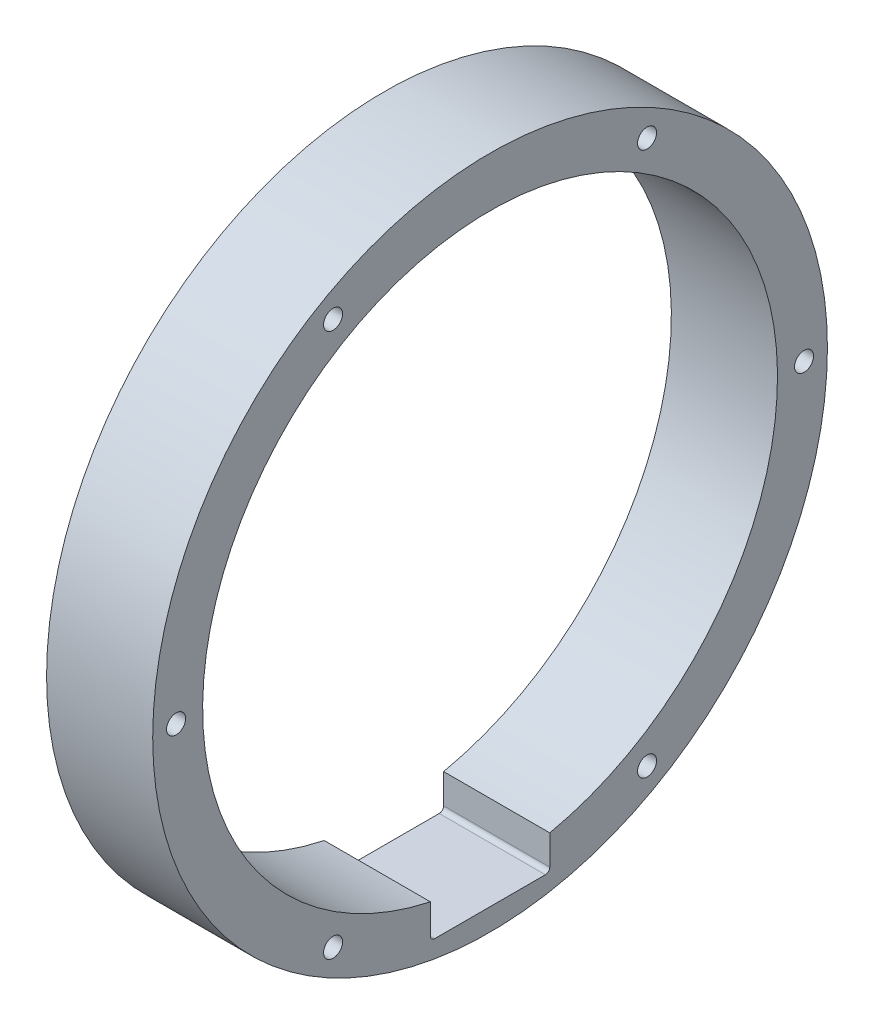
SolidWorks part; units mm, degrees
ref_plane "Front Plane" through (0, 0, 0) normal (0, 0, 1) x (1, 0, 0)
ref_plane "Top Plane" through (0, 0, 0) normal (0, 1, 0) x (1, 0, 0)
ref_plane "Right Plane" through (0, 0, 0) normal (1, 0, 0) x (0, 0, -1)
sketch "Sketch1" plane through (0, 0, 0) normal (1, 0, 0) x (0, 0, -1)
  circle A0 centre (0, 0) radius 76.29
  circle A1 centre (0, 0) radius 65
  dimension "D1" = 152.58
  dimension "D2" = 130
extrude "Boss-Extrude1" add sketch "Sketch1" along normal blind 24
sketch "Sketch2" plane through (24, 0, 0) normal (1, 0, 0) x (0, 0, -1)
  line L0 (0, -34.8517) -> (0, -97.703) construction
  line L1 (-13.5, -51.894) -> (13.5, -51.894)
  line L2 (-13.5, -51.894) -> (-13.5, -70.29)
  line L3 (-12.5, -71.29) -> (12.5, -71.29)
  line L4 (13.5, -51.894) -> (13.5, -70.29)
  circle A1 centre (0, 0) radius 76.29 construction
  arc A2 (-13.5, -70.29) -> (-12.5, -71.29) centre (-12.5, -70.29) ccw
  arc A3 (13.5, -70.29) -> (12.5, -71.29) centre (12.5, -70.29) cw
  point P6 (0, -51.894)
  point P10 (0, -76.29)
  dimension "D2" = 1
  dimension "D3" = 1
  dimension "D1" = 5
  dimension "D4" = 27
extrude "Cut-Extrude1" cut sketch "Sketch2" against normal up to next
sketch "Sketch3" plane through (24, 0, 0) normal (1, 0, 0) x (0, 0, -1)
  line L0 (-94.7404, 0) -> (95.285, 0) construction
  circle A0 centre (-71, 0) radius 2.15
  circle A1 centre (-35.5, 61.4878) radius 2.15
  circle A2 centre (35.5, 61.4878) radius 2.15
  circle A3 centre (71, 0) radius 2.15
  circle A4 centre (35.5, -61.4878) radius 2.15
  circle A5 centre (-35.5, -61.4878) radius 2.15
  point P17 (0, 0)
  dimension "D1" = 4.3
  dimension "D2" = 71
  dimension "D3" = 6
extrude "Cut-Extrude2" cut sketch "Sketch3" against normal up to next
